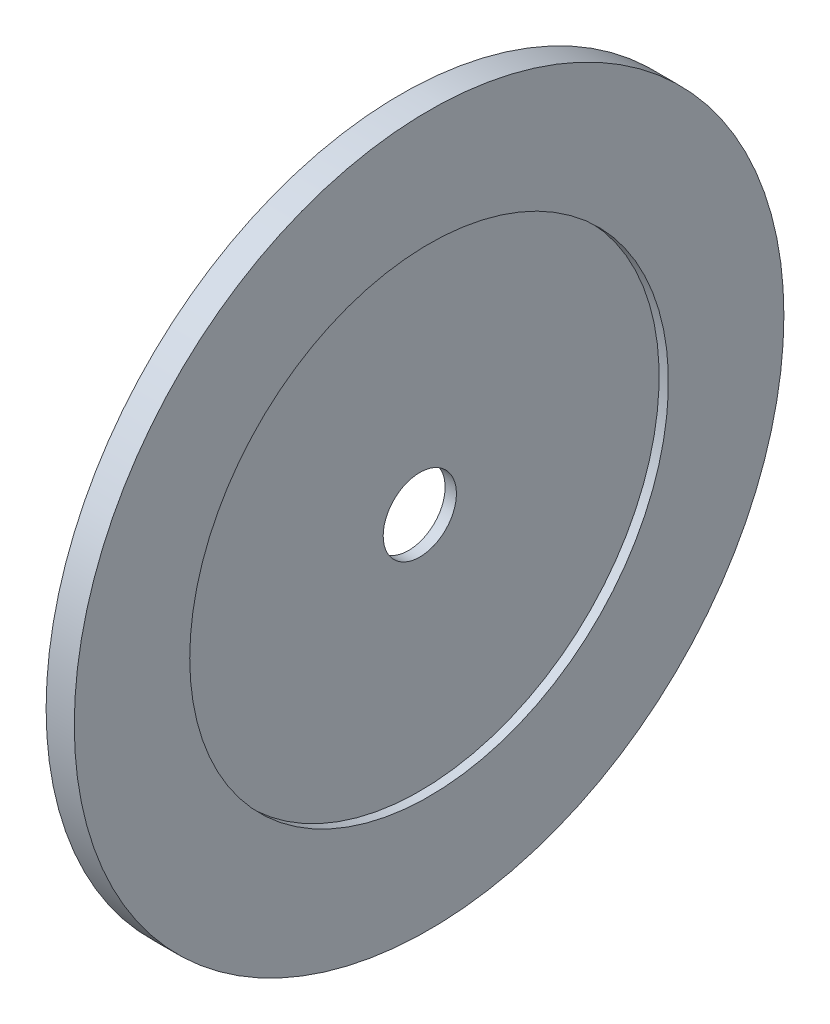
SolidWorks part; units mm, degrees
ref_plane "Front Plane" through (0, 0, 0) normal (0, 0, 1) x (1, 0, 0)
ref_plane "Top Plane" through (0, 0, 0) normal (0, 1, 0) x (1, 0, 0)
ref_plane "Right Plane" through (0, 0, 0) normal (1, 0, 0) x (0, 0, -1)
sketch "Sketch1" plane through (0, 0, 0) normal (0, 0, 1) x (1, 0, 0)
  line L0 (0, 0) -> (58.591, 0) construction
  line L2 (0, 0) -> (19, 0)
  line L3 (0, 0) -> (0, 2.5)
  line L4 (0, 2.5) -> (19, 2.5)
  line L5 (19, 0) -> (19, 2.5)
  line L6 (6.7938, 2.5) -> (6.7938, 6)
  line L11 (6.7938, 6) -> (10.7938, 6)
  line L16 (12.8938, 6) -> (12.8938, 3)
  line L17 (12.8938, 3) -> (13.8938, 3)
  line L18 (13.8938, 3) -> (13.8938, 2.5)
  line L19 (13.8938, 2.5) -> (6.7938, 2.5)
  line L22 (13.8938, 2.5) -> (16.3938, 2.5)
  line L23 (13.8938, 2.5) -> (13.8938, 4)
  line L24 (13.8938, 4) -> (16.3938, 4)
  line L25 (16.3938, 2.5) -> (16.3938, 4)
  line L27 (6.7938, 6) -> (10.7938, 6)
  line L28 (6.7938, 6) -> (6.7938, 9)
  line L29 (6.7938, 9) -> (10.7938, 9)
  line L30 (10.7938, 6) -> (10.7938, 9)
  line L31 (6.7938, 9) -> (6.7938, 8.5)
  line L32 (6.7938, 8.5) -> (5, 8.5)
  line L33 (7.8969, 22.001) -> (7.8969, 12.476) construction
  line L34 (5, 12.476) -> (10.7938, 12.476)
  line L35 (10.7938, 12.476) -> (10.7938, 9)
  line L36 (5, 7.5) -> (3, 7.5)
  line L37 (5, 8.5) -> (5, 12.476)
  line L38 (5, 7.5) -> (5, 14)
  line L39 (5, 14) -> (3, 14)
  line L40 (3, 7.5) -> (3, 14)
  line L41 (5, 22.001) -> (10.7938, 22.001)
  line L42 (5, 22.001) -> (5, 30.1625)
  line L43 (5, 30.1625) -> (10.7938, 30.1625)
  line L44 (10.7938, 22.001) -> (10.7938, 30.1625)
  line L45 (13.8938, 4) -> (13.8938, 22.001)
  line L49 (16.8938, 22.001) -> (16.8938, 8)
  line L50 (16.8938, 8) -> (17.8938, 8)
  line L51 (22.8938, 7.5) -> (22.8938, 6.5)
  line L54 (16.3938, 4) -> (13.8938, 4)
  line L55 (17.8938, 8) -> (17.8938, 7.5)
  line L56 (17.8938, 7.5) -> (22.8938, 7.5)
  line L57 (13.8938, 22.001) -> (16.8938, 22.001)
  line L58 (16.3938, 3.5) -> (19.8938, 3.5)
  line L59 (28.8938, 14) -> (26.3938, 11.5)
  line L60 (4, 31.75) -> (17.8938, 31.75)
  line L61 (17.8938, 7.5) -> (22.8938, 7.5)
  line L62 (17.8938, 7.5) -> (17.8938, 12)
  line L63 (17.8938, 12) -> (22.8938, 12)
  line L64 (22.8938, 7.5) -> (22.8938, 12)
  line L65 (17.8938, 31.75) -> (17.8938, 12)
  line L66 (22.8938, 11.5) -> (26.3938, 11.5)
  line L67 (32.8938, 23) -> (29.8938, 20)
  line L68 (33.8938, 31.5) -> (36.0538, 33.66)
  line L69 (28.8938, 14) -> (28.8938, 15)
  line L70 (28.8938, 15) -> (21.8938, 15)
  line L71 (21.8938, 15) -> (21.8938, 16)
  line L72 (21.8938, 16) -> (20.8938, 16)
  line L73 (20.8938, 16) -> (20.8938, 41)
  line L74 (19.8938, 40) -> (9.8938, 40)
  line L75 (9.8938, 40) -> (4, 40)
  line L76 (20.8938, 41) -> (19.8938, 41)
  line L77 (21.8938, 15) -> (28.8938, 15)
  line L78 (21.8938, 15) -> (21.8938, 21)
  line L79 (21.8938, 21) -> (28.8938, 21)
  line L80 (28.8938, 15) -> (28.8938, 21)
  line L81 (9.8938, 40) -> (19.8938, 40)
  line L82 (9.8938, 40) -> (9.8938, 50)
  line L83 (9.8938, 50) -> (19.8938, 50)
  line L84 (19.8938, 40) -> (19.8938, 50)
  line L85 (4, 40) -> (4, 31.75)
  line L86 (12.8938, 3) -> (12.8938, 2.5)
  line L87 (29.8938, 20) -> (28.8938, 20)
  line L88 (21.8938, 21) -> (21.8938, 63.001)
  line L89 (21.8938, 63.001) -> (24.8938, 63.001)
  line L90 (24.8938, 63.001) -> (24.8938, 26)
  line L91 (24.8938, 26) -> (25.8938, 26)
  line L92 (9.8938, 49) -> (8.65, 49)
  line L93 (8.65, 49) -> (8.65, 53.476)
  line L94 (8.65, 53.476) -> (19.8938, 53.476)
  line L95 (19.8938, 53.476) -> (19.8938, 50)
  line L96 (14.2719, 63.001) -> (14.2719, 53.476) construction
  line L97 (8.65, 63.001) -> (19.8938, 63.001)
  line L98 (8.65, 63.001) -> (8.65, 68.2625)
  line L99 (8.65, 68.2625) -> (19.8938, 68.2625)
  line L100 (19.8938, 63.001) -> (19.8938, 68.2625)
  line L101 (12.8938, 6) -> (11.8938, 6)
  line L102 (8.65, 42.5) -> (4.65, 42.5)
  line L103 (8.65, 42.5) -> (8.65, 55)
  line L104 (8.65, 55) -> (4.65, 55)
  line L105 (4.65, 42.5) -> (4.65, 55)
  line L106 (25.8938, 26) -> (25.8938, 25)
  line L107 (25.8938, 25) -> (32.8938, 25)
  line L108 (32.8938, 25) -> (32.8938, 23)
  line L109 (0, 0) -> (-2, 0)
  line L110 (0, 0) -> (0, 11)
  line L111 (25.8938, 25) -> (32.8938, 25)
  line L112 (25.8938, 25) -> (25.8938, 32.5)
  line L113 (25.8938, 32.5) -> (32.8938, 32.5)
  line L114 (32.8938, 25) -> (32.8938, 32.5)
  line L115 (33.8938, 31.5) -> (32.8938, 31.5)
  line L116 (25.8938, 32.5) -> (25.8938, 69.85)
  line L117 (25.8938, 69.85) -> (-1.35, 69.85)
  line L118 (-1.35, 69.85) -> (-1.35, 76.2)
  line L119 (-1.35, 76.2) -> (27.7938, 76.2)
  line L120 (0, 11) -> (-2, 11)
  line L121 (36.0538, 53.975) -> (28.1163, 53.975)
  line L123 (27.7938, 76.2) -> (36.0538, 67.94)
  line L124 (36.0538, 67.94) -> (36.0538, 33.66)
  line L125 (-2, 0) -> (-2, 11)
  line L126 (36.0538, 47.625) -> (28.1163, 47.625)
  line L127 (28.1163, 53.975) -> (28.1163, 47.625)
  line L128 (6.7938, 2.5) -> (6.7938, 0)
  line L129 (-0.35, 63.001) -> (-0.35, 31)
  line L132 (4.65, 63.001) -> (-0.35, 63.001)
  line L134 (-0.35, 31) -> (-1.35, 31)
  line L135 (-1.35, 31) -> (-1.35, 30)
  line L136 (-1.35, 30) -> (-11.35, 30)
  line L137 (-11.35, 30) -> (-11.35, 25.4)
  line L138 (-11.35, 25.4) -> (-2, 25.4)
  line L139 (-2, 25.4) -> (-2, 11.5)
  line L140 (-1.35, 76.2) -> (-4.35, 76.2)
  line L141 (-1.35, 30) -> (-11.35, 30)
  line L142 (-1.35, 30) -> (-1.35, 39)
  line L143 (-1.35, 39) -> (-11.35, 39)
  line L144 (-11.35, 30) -> (-11.35, 39)
  line L145 (-4.35, 76.2) -> (-12.35, 68.2)
  line L146 (-12.35, 68.2) -> (-12.35, 38)
  line L147 (-12.35, 38) -> (-11.35, 38)
  line L148 (-1.35, 39) -> (-1.35, 69.85)
  line L149 (11.8938, 6) -> (11.8938, 5.45)
  line L154 (-2, 11.5) -> (1, 11.5)
  line L155 (4.65, 60.6197) -> (23.7, 60.6197)
  line L160 (4.65, 60.6197) -> (4.65, 55.8572)
  line L161 (4.65, 55.8572) -> (23.7, 55.8572)
  line L166 (23.7, 60.6197) -> (23.7, 55.8572)
  line L167 (4.65, 60.6197) -> (23.7, 55.8572) construction
  line L172 (4.65, 55.8572) -> (23.7, 60.6197) construction
  line L173 (23.7, 62.2072) -> (24.8938, 62.2072)
  line L174 (11.8938, 5.45) -> (10.7938, 5.45)
  line L175 (10.7938, 5.45) -> (10.7938, 6)
  line L176 (23.7, 62.2072) -> (23.7, 54.2697)
  line L177 (23.7, 54.2697) -> (24.8938, 54.2697)
  line L178 (24.8938, 62.2072) -> (24.8938, 54.2697)
  line L179 (23.7, 62.2072) -> (24.8938, 54.2697) construction
  line L180 (23.7, 54.2697) -> (24.8938, 62.2072) construction
  line L181 (3, 19.6197) -> (15.7, 19.6197)
  line L182 (3, 19.6197) -> (3, 14.8572)
  line L183 (3, 14.8572) -> (15.7, 14.8572)
  line L184 (15.7, 19.6197) -> (15.7, 14.8572)
  line L185 (3, 19.6197) -> (15.7, 14.8572) construction
  line L186 (3, 14.8572) -> (15.7, 19.6197) construction
  line L187 (15.7, 21.2072) -> (16.8938, 21.2072)
  line L188 (15.7, 21.2072) -> (15.7, 13.2697)
  line L189 (15.7, 13.2697) -> (16.8938, 13.2697)
  line L190 (16.8938, 21.2072) -> (16.8938, 13.2697)
  line L191 (15.7, 21.2072) -> (16.8938, 13.2697) construction
  line L192 (15.7, 13.2697) -> (16.8938, 21.2072) construction
  line L193 (1, 11.5) -> (1, 6.5)
  line L194 (1, 6.5) -> (3, 6.5)
  line L195 (22.8938, 6.5) -> (19.8938, 3.5)
  line L196 (4.65, 63.001) -> (4.65, 42.5)
  line L197 (4.65, 42.5) -> (3, 42.5)
  line L198 (3, 42.5) -> (3, 6.5)
  line L199 (6.7938, 0) -> (12.8938, 0)
  line L200 (12.8938, 0) -> (12.8938, 2.5)
  line L201 (17.8938, 31.75) -> (17.8938, 35.875)
  line L202 (17.8938, 35.875) -> (20.8938, 35.875)
  point P7 (24.2969, 58.2385)
  point P131 (16.2969, 17.2385)
  point P135 (14.175, 58.2385)
  point P142 (0, 0)
  point P146 (9.35, 17.2385)
sketch "Sketch2" plane through (0, 0, 0) normal (0, 0, 1) x (1, 0, 0)
  line L0 (-1.35, 30) -> (-11.35, 30) construction
  line L1 (-2, 25.4) -> (-2, 11.5) construction
  line L2 (-11.35, 30) -> (-11.35, 25.4) construction
  line L3 (-11.35, 25.4) -> (-2, 25.4) construction
  line L4 (-2, 11.5) -> (1, 11.5) construction
  line L5 (1, 11.5) -> (1, 6.5) construction
  line L6 (1, 6.5) -> (3, 6.5) construction
  line L7 (3, 42.5) -> (3, 6.5) construction
  line L8 (4.65, 42.5) -> (3, 42.5) construction
  line L9 (4.65, 63.001) -> (4.65, 42.5) construction
  line L10 (4.65, 63.001) -> (-0.35, 63.001) construction
  line L11 (-0.35, 63.001) -> (-0.35, 31) construction
  line L12 (-0.35, 31) -> (-1.35, 31) construction
  line L13 (-1.35, 31) -> (-1.35, 30) construction
  line L14 (-1.35, 30) -> (-11.35, 30)
  line L15 (-2, 25.4) -> (-2, 11.5)
  line L16 (-11.35, 30) -> (-11.35, 25.4)
  line L17 (-11.35, 25.4) -> (-2, 25.4)
  line L18 (-2, 11.5) -> (1, 11.5)
  line L19 (1, 11.5) -> (1, 6.5)
  line L20 (1, 6.5) -> (3, 6.5)
  line L21 (3, 42.5) -> (3, 6.5)
  line L22 (4.65, 42.5) -> (3, 42.5)
  line L23 (4.65, 63.001) -> (4.65, 42.5)
  line L24 (4.65, 63.001) -> (-0.35, 63.001)
  line L25 (-0.35, 63.001) -> (-0.35, 31)
  line L26 (-0.35, 31) -> (-1.35, 31)
  line L27 (-1.35, 31) -> (-1.35, 30)
revolve "Revolve1" add sketch "Sketch2" angle 360 about L0 region at (0.1863, 34.915, 0)
